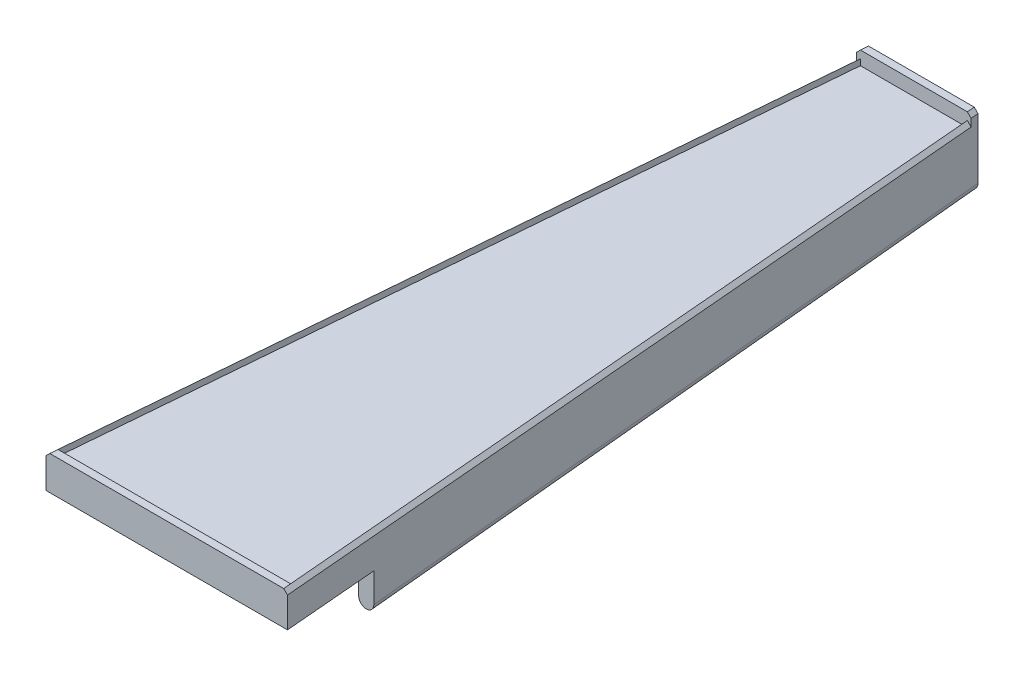
SolidWorks part; units mm, degrees
ref_plane "Front Plane" through (0, 0, 0) normal (0, 0, 1) x (1, 0, 0)
ref_plane "Top Plane" through (0, 0, 0) normal (0, 1, 0) x (1, 0, 0)
ref_plane "Right Plane" through (0, 0, 0) normal (1, 0, 0) x (0, 0, -1)
sketch "Sketch1" plane through (0, 0, 0) normal (0, 1, 0) x (1, 0, 0)
  line L0 (15, 0) -> (-15, 0)
  line L1 (0, 0) -> (0, -200) construction
  line L2 (32, -200) -> (-32, -200)
  line L3 (-32, -200) -> (-15, 0)
  line L4 (32, -200) -> (15, 0)
  dimension "\"neck length" = 200
extrude "Boss-Extrude1" add sketch "Sketch1" along normal blind 19
sketch "Sketch4" plane through (0, 0, 0) normal (1, 0, 0) x (0, 0, -1)
  line L0 (-200, 0) -> (0, 0)
  line L1 (0, 0) -> (0, 2)
  line L2 (0, 19) -> (0, 0) construction
  line L4 (0, 2) -> (-200, 0)
extrude "Cut-Extrude1" cut sketch "Sketch4" against normal through all both and the other way through all
shell "Shell1" thickness 4 removed face at (0, 1, 100)
fillet "Fillet2" 2 edges at (23.5, 1, 100) (19.4856, 1, 100) type full round first side face at (23.5, 10, 100) second side face at (19.4856, 5.5, 100) middle face at (0, 1, 100)
fillet "Fillet3" 2 edges at (-23.5, 1, 100) (-19.4856, 1, 100) type full round first side face at (-23.5, 10, 100) second side face at (-19.4856, 5.5, 100) middle face at (0.0008, 1, 100)
sketch "Sketch5" plane through (0, 19, 0) normal (0, 1, 0) x (1, 0, 0)
  line L0 (-15, 0) -> (-15.1693, -1.9912)
  line L1 (-15, 0) -> (-32, -200) construction
  line L2 (-15.1693, -1.9912) -> (15.1693, -1.9912)
  line L3 (32, -200) -> (15, 0) construction
  line L4 (15.1693, -1.9912) -> (15, 0)
  line L5 (15, 0) -> (-15, 0)
extrude "Boss-Extrude2" add sketch "Sketch5" along normal blind 2
chamfer "Chamfer1" distance 1 angle 45 2 edges at (23.5846, 19, 100.9956) (-23.5846, 19, 100.9956)
chamfer "Chamfer2" distance 1 angle 45 2 edges at (15.0846, 21, 0.9956) (-15.0846, 21, 0.9956)
sketch "Sketch6" plane through (0, 19, 0) normal (0, 1, 0) x (1, 0, 0)
  line L0 (-14.1656, -1.9912) -> (14.1656, -1.9912)
  line L1 (0, -1.9912) -> (0, -197.9912) construction
  line L2 (-30.8256, -197.9912) -> (30.8256, -197.9912)
  line L3 (30.9964, -200) -> (14.1656, -1.9912) construction
  line L4 (30.8256, -197.9912) -> (14.1656, -1.9912)
  line L5 (-14.1656, -1.9912) -> (-30.8256, -197.9912)
  line L6 (-14.1656, -1.9912) -> (-30.9964, -200) construction
extrude "Cut-Extrude2" cut sketch "Sketch6" against normal blind 1.6
sketch "Sketch7" plane through (0, 0, 200) normal (0, 0, 1) x (1, 0, 0)
  line L1 (-32, 9.9992) -> (32, 9.9992)
  line L2 (-32, 18) -> (-32, 1.9984) construction
  line L3 (32, 18) -> (32, 1.9984) construction
  line L4 (32, 9.9992) -> (32, 0)
  line L7 (-32, 0) -> (-32, 9.9992)
  line L8 (-32, 0) -> (32, 0)
extrude "Cut-Extrude3" cut sketch "Sketch7" against normal blind 25
equation "\"neck length\"= 200mm"
